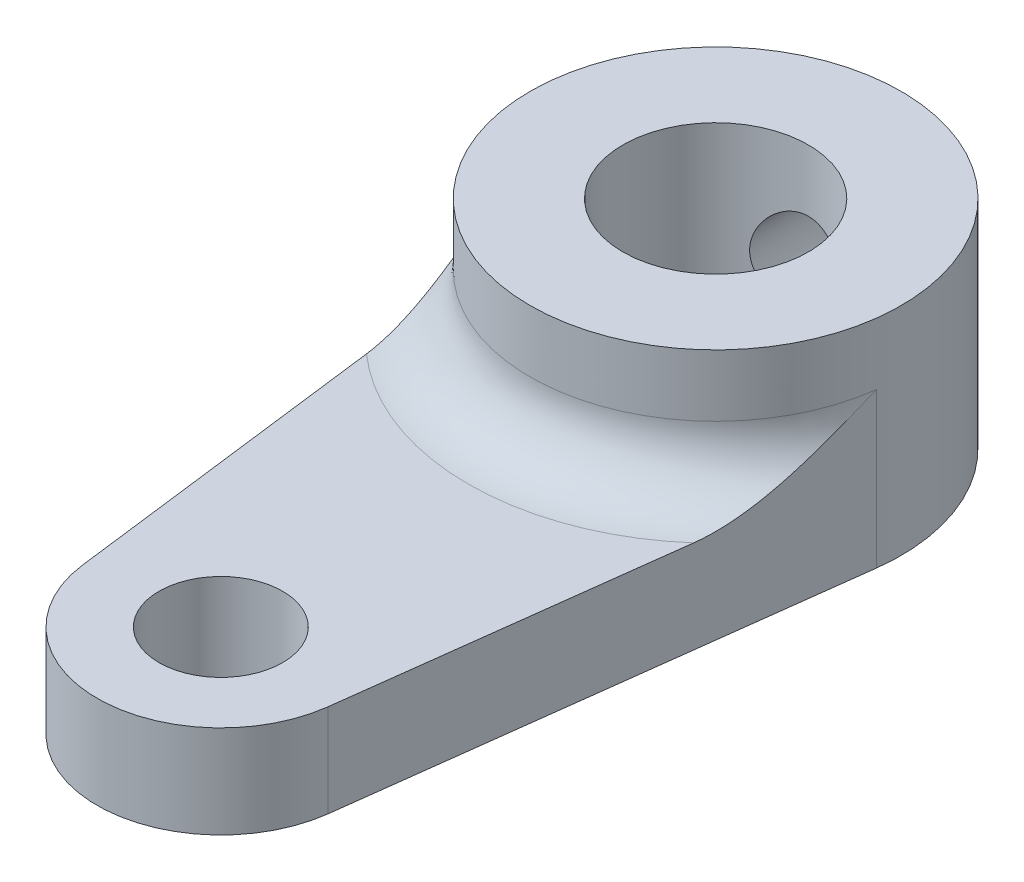
SolidWorks part; units mm, degrees
note: The reader was unsure of these and kept them because the rebuilt part matched: shared geometry of "Sketch1<3>".
ref_plane "Front Plane" through (0, 0, 0) normal (0, 0, 1) x (1, 0, 0)
ref_plane "Top Plane" through (0, 0, 0) normal (0, 1, 0) x (1, 0, 0)
ref_plane "Right Plane" through (0, 0, 0) normal (1, 0, 0) x (0, 0, -1)
sketch "Sketch1" plane through (0, 0, 0) normal (0, 1, 0) x (1, 0, 0)
  line L0 (0, 0) -> (0, -16) construction
  line L1 (-5.9529, -0.75) -> (-3.9686, -16.5)
  line L2 (5.9529, -0.75) -> (3.9686, -16.5)
  circle A0 centre (0, 0) radius 6
  circle A2 centre (0, -16) radius 4
  circle A3 centre (0, -16) radius 2
  circle A4 centre (0, 0) radius 3
  dimension "D1" = 12
  dimension "D2" = 4
  dimension "D3" = 8
  dimension "D5" = 6
  dimension "D4" = 16
extrude "Boss-Extrude1" add sketch "Sketch1" along normal blind 3
extrude "Boss-Extrude2" add sketch "Sketch1<3>" along normal blind 4 from offset 3
sketch "Sketch1<3>" plane through (0, 0, 0) normal (0, 1, 0) x (1, 0, 0) same geometry as "Sketch1"
fillet "Fillet1" radius 2 1 edges at (0, 3, 6)
sketch "Sketch2" plane through (0, 0, 0) normal (0, -1, 0) x (1, 0, 0)
  line L0 (-7.1253, -7) -> (6.0354, -7)
  dimension "D1" = 7
  dimension "D2" = 13.1607
surface "Surface-Extrude1" sketch "Sketch2" parameters "D1"=7
hole_wizard "M3 Tapped Hole1" positions "Sketch3" profile "Sketch4" tap size "M3" standard "ISO"
sketch "Sketch3" plane through (0, 0, -7) normal (0, 0, 1) x (1, 0, 0)
  point P0 (0, 3.5)
  dimension "D1" = 3.5
sketch "Sketch4" plane through (0, 3.5, -7) normal (1, 0, 0) x (0, 1, 0)
  line L0 (0, 0) -> (0, 9.4013)
  line L1 (0, 9.4013) -> (1.5, 8.5)
  line L2 (1.5, 8.5) -> (1.5, 0.025)
  line L3 (1.5, 0.025) -> (1.525, 0)
  line L5 (1.525, 0) -> (0, 0)
  line L6 (-1.5, 0.025) -> (-1.525, 0) construction
  line L10 (0, 9.4013) -> (-1.5, 8.5) construction
  line L11 (0, -6.35) -> (0, 107.95) construction
  dimension "Tap Drill Dia." = 3
  dimension "Tap Drill Depth" = 8.5
  dimension "Near C'Sink Dia." = 3.05
  dimension "Near C'Sink Angle" = 90
  dimension "Drill Angle" = 118
cosmetic thread "Hole Thread1" parameters "D1"=4.4019, "D2"=3
